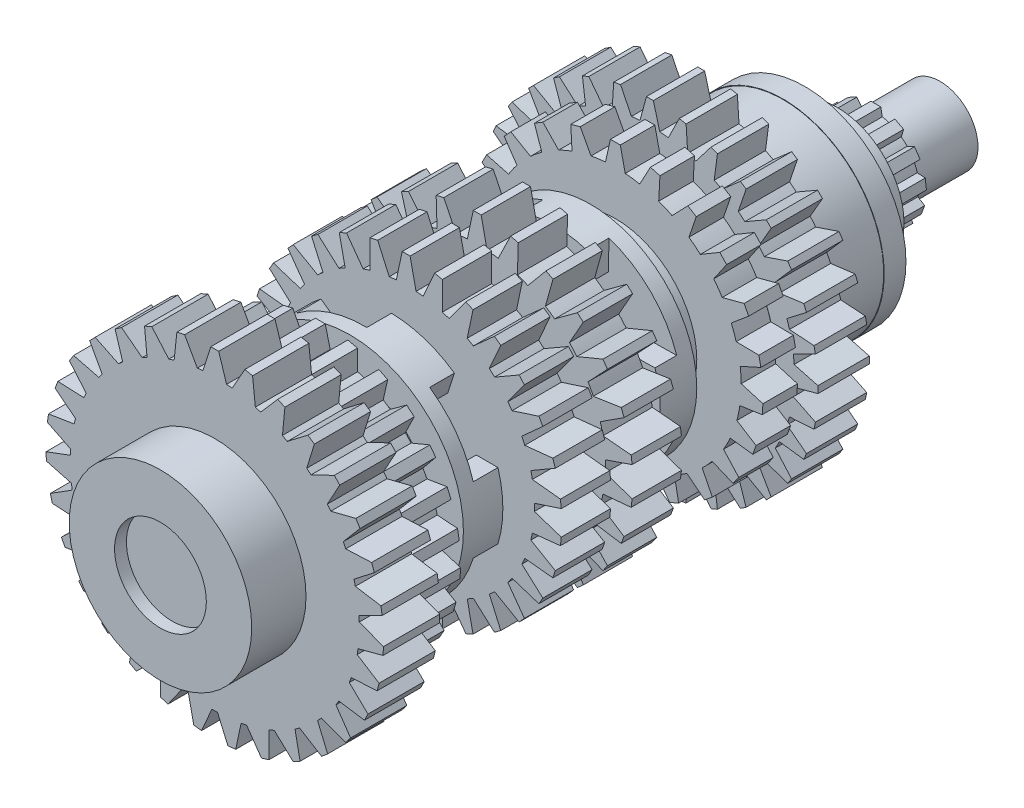
SolidWorks part; units mm, degrees
material "Plain Carbon Steel"
ref_plane "Front Plane" through (0, 0, 0) normal (0, 0, 1) x (1, 0, 0)
ref_plane "Top Plane" through (0, 0, 0) normal (0, 1, 0) x (1, 0, 0)
ref_plane "Right Plane" through (0, 0, 0) normal (1, 0, 0) x (0, 0, -1)
sketch "Sketch1" plane through (0, 0, 0) normal (0, 0, 1) x (1, 0, 0)
  circle A0 centre (0, 0) radius 9.779
  dimension "D1" = 19.558
extrude "Boss-Extrude1" add sketch "Sketch1" along normal blind 16.51
sketch "Sketch2" plane through (0, 0, 16.51) normal (0, 0, 1) x (1, 0, 0)
  line L0 (-1.651, 10.925) -> (-1.27, 12.957)
  line L1 (-1.27, 12.957) -> (1.27, 12.957)
  line L2 (1.27, 12.957) -> (1.651, 10.925)
  line L3 (0, 0) -> (0, 25.9139) construction
  line L4 (3.6152, 10.4408) -> (4.8969, 12.063)
  line L5 (4.8969, 12.063) -> (7.1459, 10.8826)
  line L6 (7.1459, 10.8826) -> (6.539, 8.9063)
  line L7 (8.0532, 7.5648) -> (9.9419, 8.4056)
  line L8 (9.9419, 8.4056) -> (11.3848, 6.3152)
  line L9 (11.3848, 6.3152) -> (9.9289, 4.8473)
  line L10 (10.6463, 2.9558) -> (12.7094, 2.8225)
  line L11 (12.7094, 2.8225) -> (13.0156, 0.301)
  line L12 (13.0156, 0.301) -> (11.0443, -0.3221)
  line L13 (10.8005, -2.3303) -> (12.5653, -3.4071)
  line L14 (12.5653, -3.4071) -> (11.6646, -5.7821)
  line L15 (11.6646, -5.7821) -> (9.6296, -5.4178)
  line L16 (8.4804, -7.0826) -> (9.5427, -8.8563)
  line L17 (9.5427, -8.8563) -> (7.6414, -10.5406)
  line L18 (7.6414, -10.5406) -> (6.0088, -9.2723)
  line L19 (4.2175, -10.2124) -> (4.3339, -12.2765)
  line L20 (4.3339, -12.2765) -> (1.8677, -12.8844)
  line L21 (1.8677, -12.8844) -> (1.0115, -11.0026)
  line L22 (-1.0115, -11.0026) -> (-1.8677, -12.8844)
  line L23 (-1.8677, -12.8844) -> (-4.3339, -12.2765)
  line L24 (-4.3339, -12.2765) -> (-4.2175, -10.2124)
  line L25 (-6.0088, -9.2723) -> (-7.6414, -10.5406)
  line L26 (-7.6414, -10.5406) -> (-9.5427, -8.8563)
  line L27 (-9.5427, -8.8563) -> (-8.4804, -7.0826)
  line L28 (-9.6296, -5.4178) -> (-11.6646, -5.7821)
  line L29 (-11.6646, -5.7821) -> (-12.5653, -3.4071)
  line L30 (-12.5653, -3.4071) -> (-10.8005, -2.3303)
  line L31 (-11.0443, -0.3221) -> (-13.0156, 0.301)
  line L32 (-13.0156, 0.301) -> (-12.7094, 2.8225)
  line L33 (-12.7094, 2.8225) -> (-10.6463, 2.9558)
  line L34 (-9.9289, 4.8473) -> (-11.3848, 6.3152)
  line L35 (-11.3848, 6.3152) -> (-9.9419, 8.4056)
  line L36 (-9.9419, 8.4056) -> (-8.0532, 7.5648)
  line L37 (-6.539, 8.9063) -> (-7.1459, 10.8826)
  line L38 (-7.1459, 10.8826) -> (-4.8969, 12.063)
  line L39 (-4.8969, 12.063) -> (-3.6152, 10.4408)
  arc A0 (-1.651, 10.925) -> (-3.6152, 10.4408) centre (0, 0) ccw
  circle A1 centre (0, 0) radius 9.779 construction
  arc A2 (3.6152, 10.4408) -> (1.651, 10.925) centre (0, 0) ccw
  arc A3 (8.0532, 7.5648) -> (6.539, 8.9063) centre (0, 0) ccw
  arc A4 (10.6463, 2.9558) -> (9.9289, 4.8473) centre (0, 0) ccw
  arc A5 (10.8005, -2.3303) -> (11.0443, -0.3221) centre (0, 0) ccw
  arc A6 (8.4804, -7.0826) -> (9.6296, -5.4178) centre (0, 0) ccw
  arc A7 (4.2175, -10.2124) -> (6.0088, -9.2723) centre (0, 0) ccw
  arc A8 (-1.0115, -11.0026) -> (1.0115, -11.0026) centre (0, 0) ccw
  arc A9 (-6.0088, -9.2723) -> (-4.2175, -10.2124) centre (0, 0) ccw
  arc A10 (-9.6296, -5.4178) -> (-8.4804, -7.0826) centre (0, 0) ccw
  arc A11 (-11.0443, -0.3221) -> (-10.8005, -2.3303) centre (0, 0) ccw
  arc A12 (-9.9289, 4.8473) -> (-10.6463, 2.9558) centre (0, 0) ccw
  arc A13 (-6.539, 8.9063) -> (-8.0532, 7.5648) centre (0, 0) ccw
  point P12 (0, 12.957)
  point P62 (0, 0)
  dimension "D1" = 1.27
  dimension "D2" = 1.651
  dimension "D3" = 2.54
  dimension "D4" = 2.032
  dimension "D5" = 1.651
  dimension "D6" = 13
extrude "Boss-Extrude2" add sketch "Sketch2" along normal blind 9.906
sketch "Sketch3" plane through (0, 0, 26.416) normal (0, 0, 1) x (1, 0, 0)
  circle A0 centre (0, 0) radius 17.145
  dimension "D1" = 34.29
extrude "Boss-Extrude3" add sketch "Sketch3" along normal blind 13.97
ref_plane "Plane1" through (0, 0, 34.798) normal (0, 0, 1) x (1, 0, 0)
sketch "Sketch4" plane through (0, 0, 34.798) normal (0, 0, 1) x (1, 0, 0)
  circle A0 centre (0, 0) radius 17.145
  circle A1 centre (0, 0) radius 26.035
  dimension "D1" = 52.07
  dimension "D2" = 34.29
extrude "Boss-Extrude4" add sketch "Sketch4" along normal blind 5.588
sketch "Sketch5" plane through (0, 0, 40.386) normal (0, 0, 1) x (1, 0, 0)
  circle A0 centre (0, 0) radius 25.908
  dimension "D1" = 51.816
extrude "Boss-Extrude5" add sketch "Sketch5" along normal blind 19.05
sketch "Sketch6" plane through (0, 0, 59.436) normal (0, 0, 1) x (1, 0, 0)
  circle A0 centre (0, 0) radius 17.78
  dimension "D1" = 35.56
extrude "Boss-Extrude6" add sketch "Sketch6" along normal blind 2.032
sketch "Sketch8" plane through (0, 0, 61.468) normal (0, 0, 1) x (1, 0, 0)
  line L0 (0, 0) -> (0, 86.5116) construction
  line L1 (0, -28.6385) -> (0, 28.6385) construction
  line L2 (-2.54, 37.1242) -> (-0.889, 43.2558)
  line L3 (-0.889, 43.2558) -> (0.889, 43.2558)
  line L4 (0.889, 43.2558) -> (2.54, 37.1242)
  line L5 (4.7514, 36.9064) -> (7.5669, 42.5981)
  line L6 (9.3107, 42.2512) -> (9.7338, 35.9153)
  line L7 (7.5669, 42.5981) -> (9.3107, 42.2512)
  line L8 (11.8602, 35.2703) -> (15.732, 40.3034)
  line L9 (17.3746, 39.623) -> (16.5535, 33.3263)
  line L10 (15.732, 40.3034) -> (17.3746, 39.623)
  line L11 (18.5132, 32.2788) -> (23.2925, 36.4598)
  line L12 (24.7708, 35.472) -> (22.737, 29.4565)
  line L13 (23.2925, 36.4598) -> (24.7708, 35.472)
  line L14 (24.4547, 28.0468) -> (29.9579, 31.2151)
  line L15 (31.2151, 29.9579) -> (28.0468, 24.4547)
  line L16 (29.9579, 31.2151) -> (31.2151, 29.9579)
  line L17 (29.4565, 22.737) -> (35.472, 24.7708)
  line L18 (36.4598, 23.2925) -> (32.2788, 18.5132)
  line L19 (35.472, 24.7708) -> (36.4598, 23.2925)
  line L20 (33.3263, 16.5535) -> (39.623, 17.3746)
  line L21 (40.3034, 15.732) -> (35.2703, 11.8602)
  line L22 (39.623, 17.3746) -> (40.3034, 15.732)
  line L23 (35.9153, 9.7338) -> (42.2512, 9.3107)
  line L24 (42.5981, 7.5669) -> (36.9064, 4.7514)
  line L25 (42.2512, 9.3107) -> (42.5981, 7.5669)
  line L26 (37.1242, 2.54) -> (43.2558, 0.889)
  line L27 (43.2558, -0.889) -> (37.1242, -2.54)
  line L28 (43.2558, 0.889) -> (43.2558, -0.889)
  line L29 (36.9064, -4.7514) -> (42.5981, -7.5669)
  line L30 (42.2512, -9.3107) -> (35.9153, -9.7338)
  line L31 (42.5981, -7.5669) -> (42.2512, -9.3107)
  line L32 (35.2703, -11.8602) -> (40.3034, -15.732)
  line L33 (39.623, -17.3746) -> (33.3263, -16.5535)
  line L34 (40.3034, -15.732) -> (39.623, -17.3746)
  line L35 (32.2788, -18.5132) -> (36.4598, -23.2925)
  line L36 (35.472, -24.7708) -> (29.4565, -22.737)
  line L37 (36.4598, -23.2925) -> (35.472, -24.7708)
  line L38 (28.0468, -24.4547) -> (31.2151, -29.9579)
  line L39 (29.9579, -31.2151) -> (24.4547, -28.0468)
  line L40 (31.2151, -29.9579) -> (29.9579, -31.2151)
  line L41 (22.737, -29.4565) -> (24.7708, -35.472)
  line L42 (23.2925, -36.4598) -> (18.5132, -32.2788)
  line L43 (24.7708, -35.472) -> (23.2925, -36.4598)
  line L44 (16.5535, -33.3263) -> (17.3746, -39.623)
  line L45 (15.732, -40.3034) -> (11.8602, -35.2703)
  line L46 (17.3746, -39.623) -> (15.732, -40.3034)
  line L47 (9.7338, -35.9153) -> (9.3107, -42.2512)
  line L48 (7.5669, -42.5981) -> (4.7514, -36.9064)
  line L49 (9.3107, -42.2512) -> (7.5669, -42.5981)
  line L50 (2.54, -37.1242) -> (0.889, -43.2558)
  line L51 (-0.889, -43.2558) -> (-2.54, -37.1242)
  line L52 (0.889, -43.2558) -> (-0.889, -43.2558)
  line L53 (-4.7514, -36.9064) -> (-7.5669, -42.5981)
  line L54 (-9.3107, -42.2512) -> (-9.7338, -35.9153)
  line L55 (-7.5669, -42.5981) -> (-9.3107, -42.2512)
  line L56 (-11.8602, -35.2703) -> (-15.732, -40.3034)
  line L57 (-17.3746, -39.623) -> (-16.5535, -33.3263)
  line L58 (-15.732, -40.3034) -> (-17.3746, -39.623)
  line L59 (-18.5132, -32.2788) -> (-23.2925, -36.4598)
  line L60 (-24.7708, -35.472) -> (-22.737, -29.4565)
  line L61 (-23.2925, -36.4598) -> (-24.7708, -35.472)
  line L62 (-24.4547, -28.0468) -> (-29.9579, -31.2151)
  line L63 (-31.2151, -29.9579) -> (-28.0468, -24.4547)
  line L64 (-29.9579, -31.2151) -> (-31.2151, -29.9579)
  line L65 (-29.4565, -22.737) -> (-35.472, -24.7708)
  line L66 (-36.4598, -23.2925) -> (-32.2788, -18.5132)
  line L67 (-35.472, -24.7708) -> (-36.4598, -23.2925)
  line L68 (-33.3263, -16.5535) -> (-39.623, -17.3746)
  line L69 (-40.3034, -15.732) -> (-35.2703, -11.8602)
  line L70 (-39.623, -17.3746) -> (-40.3034, -15.732)
  line L71 (-35.9153, -9.7338) -> (-42.2512, -9.3107)
  line L72 (-42.5981, -7.5669) -> (-36.9064, -4.7514)
  line L73 (-42.2512, -9.3107) -> (-42.5981, -7.5669)
  line L74 (-37.1242, -2.54) -> (-43.2558, -0.889)
  line L75 (-43.2558, 0.889) -> (-37.1242, 2.54)
  line L76 (-43.2558, -0.889) -> (-43.2558, 0.889)
  line L77 (-36.9064, 4.7514) -> (-42.5981, 7.5669)
  line L78 (-42.2512, 9.3107) -> (-35.9153, 9.7338)
  line L79 (-42.5981, 7.5669) -> (-42.2512, 9.3107)
  line L80 (-35.2703, 11.8602) -> (-40.3034, 15.732)
  line L81 (-39.623, 17.3746) -> (-33.3263, 16.5535)
  line L82 (-40.3034, 15.732) -> (-39.623, 17.3746)
  line L83 (-32.2788, 18.5132) -> (-36.4598, 23.2925)
  line L84 (-35.472, 24.7708) -> (-29.4565, 22.737)
  line L85 (-36.4598, 23.2925) -> (-35.472, 24.7708)
  line L86 (-28.0468, 24.4547) -> (-31.2151, 29.9579)
  line L87 (-29.9579, 31.2151) -> (-24.4547, 28.0468)
  line L88 (-31.2151, 29.9579) -> (-29.9579, 31.2151)
  line L89 (-22.737, 29.4565) -> (-24.7708, 35.472)
  line L90 (-23.2925, 36.4598) -> (-18.5132, 32.2788)
  line L91 (-24.7708, 35.472) -> (-23.2925, 36.4598)
  line L92 (-16.5535, 33.3263) -> (-17.3746, 39.623)
  line L93 (-15.732, 40.3034) -> (-11.8602, 35.2703)
  line L94 (-17.3746, 39.623) -> (-15.732, 40.3034)
  line L95 (-9.7338, 35.9153) -> (-9.3107, 42.2512)
  line L96 (-7.5669, 42.5981) -> (-4.7514, 36.9064)
  line L97 (-9.3107, 42.2512) -> (-7.5669, 42.5981)
  arc A0 (-2.54, 37.1242) -> (-4.7514, 36.9064) centre (0, 0) ccw
  arc A1 (4.7514, 36.9064) -> (2.54, 37.1242) centre (0, 0) ccw
  arc A2 (11.8602, 35.2703) -> (9.7338, 35.9153) centre (0, 0) ccw
  arc A3 (18.5132, 32.2788) -> (16.5535, 33.3263) centre (0, 0) ccw
  arc A4 (24.4547, 28.0468) -> (22.737, 29.4565) centre (0, 0) ccw
  arc A5 (-9.7338, 35.9153) -> (-11.8602, 35.2703) centre (0, 0) ccw
  arc A6 (-16.5535, 33.3263) -> (-18.5132, 32.2788) centre (0, 0) ccw
  arc A7 (-22.737, 29.4565) -> (-24.4547, 28.0468) centre (0, 0) ccw
  arc A8 (-28.0468, 24.4547) -> (-29.4565, 22.737) centre (0, 0) ccw
  arc A9 (-32.2788, 18.5132) -> (-33.3263, 16.5535) centre (0, 0) ccw
  arc A10 (-35.2703, 11.8602) -> (-35.9153, 9.7338) centre (0, 0) ccw
  arc A11 (-36.9064, 4.7514) -> (-37.1242, 2.54) centre (0, 0) ccw
  arc A12 (-37.1242, -2.54) -> (-36.9064, -4.7514) centre (0, 0) ccw
  arc A13 (-35.9153, -9.7338) -> (-35.2703, -11.8602) centre (0, 0) ccw
  arc A14 (-33.3263, -16.5535) -> (-32.2788, -18.5132) centre (0, 0) ccw
  arc A15 (-29.4565, -22.737) -> (-28.0468, -24.4547) centre (0, 0) ccw
  arc A16 (-24.4547, -28.0468) -> (-22.737, -29.4565) centre (0, 0) ccw
  arc A17 (-18.5132, -32.2788) -> (-16.5535, -33.3263) centre (0, 0) ccw
  arc A18 (-11.8602, -35.2703) -> (-9.7338, -35.9153) centre (0, 0) ccw
  arc A19 (-4.7514, -36.9064) -> (-2.54, -37.1242) centre (0, 0) ccw
  arc A20 (2.54, -37.1242) -> (4.7514, -36.9064) centre (0, 0) ccw
  arc A21 (9.7338, -35.9153) -> (11.8602, -35.2703) centre (0, 0) ccw
  arc A22 (16.5535, -33.3263) -> (18.5132, -32.2788) centre (0, 0) ccw
  arc A23 (22.737, -29.4565) -> (24.4547, -28.0468) centre (0, 0) ccw
  arc A24 (28.0468, -24.4547) -> (29.4565, -22.737) centre (0, 0) ccw
  arc A25 (32.2788, -18.5132) -> (33.3263, -16.5535) centre (0, 0) ccw
  arc A26 (35.2703, -11.8602) -> (35.9153, -9.7338) centre (0, 0) ccw
  arc A27 (36.9064, -4.7514) -> (37.1242, -2.54) centre (0, 0) ccw
  arc A28 (37.1242, 2.54) -> (36.9064, 4.7514) centre (0, 0) ccw
  arc A29 (35.9153, 9.7338) -> (35.2703, 11.8602) centre (0, 0) ccw
  arc A30 (33.3263, 16.5535) -> (32.2788, 18.5132) centre (0, 0) ccw
  arc A31 (29.4565, 22.737) -> (28.0468, 24.4547) centre (0, 0) ccw
  point P8 (0, 43.2558)
  point P138 (0, 0)
  dimension "D1" = 74.422
  dimension "D2" = 2.54
  dimension "D3" = 2.54
  dimension "D4" = 1.778
  dimension "D5" = 6.35
  dimension "D6" = 32
extrude "Boss-Extrude7" add sketch "Sketch8" along normal blind 13.208
sketch "Sketch10" plane through (0, 0, 74.676) normal (0, 0, 1) x (1, 0, 0)
  line L0 (-12.7, 27.0822) -> (-8.89, 19.05)
  line L1 (8.89, 19.05) -> (12.7, 27.0822)
  line L2 (0, 0) -> (0, 67.7318) construction
  line L3 (0, -41.0718) -> (0, 41.0718) construction
  line L4 (21.8322, 20.4473) -> (15.3705, 14.3417)
  line L5 (20.8648, -2.5681) -> (29.6812, -3.7096)
  line L6 (26.193, -14.4451) -> (18.3895, -10.1864)
  line L7 (4.0051, -20.6372) -> (5.644, -29.3748)
  line L8 (-5.644, -29.3748) -> (-4.0051, -20.6372)
  line L9 (-18.3895, -10.1864) -> (-26.193, -14.4451)
  line L10 (-29.6812, -3.7096) -> (-20.8648, -2.5681)
  line L11 (-15.3705, 14.3417) -> (-21.8322, 20.4473)
  arc A3 (-8.89, 19.05) -> (8.89, 19.05) centre (0, -7.438) cw
  arc A4 (-12.7, 27.0822) -> (12.7, 27.0822) centre (0, 14.6388) cw
  arc A5 (21.8322, 20.4473) -> (29.6812, -3.7096) centre (13.9223, 4.5236) cw
  arc A6 (15.3705, 14.3417) -> (20.8648, -2.5681) centre (-7.0739, -2.2985) cw
  arc A7 (26.193, -14.4451) -> (5.644, -29.3748) centre (8.6045, -11.843) cw
  arc A8 (18.3895, -10.1864) -> (4.0051, -20.6372) centre (-4.3719, 6.0174) cw
  arc A9 (-5.644, -29.3748) -> (-26.193, -14.4451) centre (-8.6045, -11.843) cw
  arc A10 (-4.0051, -20.6372) -> (-18.3895, -10.1864) centre (4.3719, 6.0174) cw
  arc A11 (-29.6812, -3.7096) -> (-21.8322, 20.4473) centre (-13.9223, 4.5236) cw
  arc A12 (-20.8648, -2.5681) -> (-15.3705, 14.3417) centre (7.0739, -2.2985) cw
  point P5 (0, 20.502)
  point P39 (0, 0)
  dimension "D3" = 19.05
  dimension "D4" = 17.78
  dimension "D5" = 27.94
  dimension "D1" = 8.89
  dimension "D2" = 8.89
  dimension "D6" = 17.78
  dimension "D7" = 25.4
  dimension "D8" = 5
extrude "Cut-Extrude1" cut sketch "Sketch10" against normal up to surface (13.208 mm away) up to face at (17.78, 0, 61.468)
sketch "Sketch12" plane through (0, 0, 74.676) normal (0, 0, 1) x (1, 0, 0)
  line L0 (-2.54, 32.2852) -> (-1.27, 37.9875)
  line L1 (-1.27, 37.9875) -> (1.27, 37.9875)
  line L2 (1.27, 37.9875) -> (2.54, 32.2852)
  line L3 (0, 0) -> (0, 75.975) construction
  line L4 (11.4718, 36.2362) -> (11.1563, 30.4027)
  line L5 (6.2646, 31.7733) -> (9.026, 36.9215)
  line L6 (9.026, 36.9215) -> (11.4718, 36.2362)
  line L7 (20.8228, 31.7974) -> (18.9451, 26.2654)
  line L8 (14.6047, 28.9049) -> (18.6526, 33.1171)
  line L9 (18.6526, 33.1171) -> (20.8228, 31.7974)
  line L10 (28.6295, 25.0003) -> (25.3289, 20.1801)
  line L11 (21.8615, 23.8927) -> (26.8958, 26.8567)
  line L12 (26.8958, 26.8567) -> (28.6295, 25.0003)
  line L13 (34.3128, 16.3491) -> (29.8342, 12.5981)
  line L14 (27.497, 17.1085) -> (33.1443, 18.6043)
  line L15 (33.1443, 18.6043) -> (34.3128, 16.3491)
  line L16 (37.4514, 6.4854) -> (32.1267, 4.0818)
  line L17 (31.0932, 9.0555) -> (36.9346, 8.9722)
  line L18 (36.9346, 8.9722) -> (37.4514, 6.4854)
  line L19 (37.8123, -3.8594) -> (32.0366, -4.7373)
  line L20 (32.3833, 0.3309) -> (37.9856, -1.3253)
  line L21 (37.9856, -1.3253) -> (37.8123, -3.8594)
  line L22 (35.3689, -13.9179) -> (29.5705, -13.205)
  line L23 (31.2717, -8.4183) -> (36.2195, -11.5246)
  line L24 (36.2195, -11.5246) -> (35.3689, -13.9179)
  line L25 (30.3023, -22.9442) -> (24.9113, -20.6934)
  line L26 (27.8408, -16.5432) -> (31.767, -20.8691)
  line L27 (31.767, -20.8691) -> (30.3023, -22.9442)
  line L28 (22.9883, -30.2688) -> (18.4045, -26.647)
  line L29 (22.3451, -23.4411) -> (24.9586, -28.6659)
  line L30 (24.9586, -28.6659) -> (22.9883, -30.2688)
  line L31 (13.9694, -35.3486) -> (10.5328, -30.6243)
  line L32 (15.1922, -28.6004) -> (16.2991, -34.3366)
  line L33 (16.2991, -34.3366) -> (13.9694, -35.3486)
  line L34 (3.9145, -37.8066) -> (1.8798, -32.3304)
  line L35 (6.9125, -31.6387) -> (6.4308, -37.4608)
  line L36 (6.4308, -37.4608) -> (3.9145, -37.8066)
  line L37 (-6.4308, -37.4608) -> (-6.9125, -31.6387)
  line L38 (-1.8798, -32.3304) -> (-3.9145, -37.8066)
  line L39 (-3.9145, -37.8066) -> (-6.4308, -37.4608)
  line L40 (-16.2991, -34.3366) -> (-15.1922, -28.6004)
  line L41 (-10.5328, -30.6243) -> (-13.9694, -35.3486)
  line L42 (-13.9694, -35.3486) -> (-16.2991, -34.3366)
  line L43 (-24.9586, -28.6659) -> (-22.3451, -23.4411)
  line L44 (-18.4045, -26.647) -> (-22.9883, -30.2688)
  line L45 (-22.9883, -30.2688) -> (-24.9586, -28.6659)
  line L46 (-31.767, -20.8691) -> (-27.8408, -16.5432)
  line L47 (-24.9113, -20.6934) -> (-30.3023, -22.9442)
  line L48 (-30.3023, -22.9442) -> (-31.767, -20.8691)
  line L49 (-36.2195, -11.5246) -> (-31.2717, -8.4183)
  line L50 (-29.5705, -13.205) -> (-35.3689, -13.9179)
  line L51 (-35.3689, -13.9179) -> (-36.2195, -11.5246)
  line L52 (-37.9856, -1.3253) -> (-32.3833, 0.3309)
  line L53 (-32.0366, -4.7373) -> (-37.8123, -3.8594)
  line L54 (-37.8123, -3.8594) -> (-37.9856, -1.3253)
  line L55 (-36.9346, 8.9722) -> (-31.0932, 9.0555)
  line L56 (-32.1267, 4.0818) -> (-37.4514, 6.4854)
  line L57 (-37.4514, 6.4854) -> (-36.9346, 8.9722)
  line L58 (-33.1443, 18.6043) -> (-27.497, 17.1085)
  line L59 (-29.8342, 12.5981) -> (-34.3128, 16.3491)
  line L60 (-34.3128, 16.3491) -> (-33.1443, 18.6043)
  line L61 (-26.8958, 26.8567) -> (-21.8615, 23.8927)
  line L62 (-25.3289, 20.1801) -> (-28.6295, 25.0003)
  line L63 (-28.6295, 25.0003) -> (-26.8958, 26.8567)
  line L64 (-18.6526, 33.1171) -> (-14.6047, 28.9049)
  line L65 (-18.9451, 26.2654) -> (-20.8228, 31.7974)
  line L66 (-20.8228, 31.7974) -> (-18.6526, 33.1171)
  line L67 (-9.026, 36.9215) -> (-6.2646, 31.7733)
  line L68 (-11.1563, 30.4027) -> (-11.4718, 36.2362)
  line L69 (-11.4718, 36.2362) -> (-9.026, 36.9215)
  arc A0 (-2.54, 32.2852) -> (-6.2646, 31.7733) centre (0, 0) ccw
  arc A1 (6.2646, 31.7733) -> (2.54, 32.2852) centre (0, 0) ccw
  arc A2 (14.6047, 28.9049) -> (11.1563, 30.4027) centre (0, 0) ccw
  arc A3 (21.8615, 23.8927) -> (18.9451, 26.2654) centre (0, 0) ccw
  arc A4 (27.497, 17.1085) -> (25.3289, 20.1801) centre (0, 0) ccw
  arc A5 (31.0932, 9.0555) -> (29.8342, 12.5981) centre (0, 0) ccw
  arc A6 (32.3833, 0.3309) -> (32.1267, 4.0818) centre (0, 0) ccw
  arc A7 (31.2717, -8.4183) -> (32.0366, -4.7373) centre (0, 0) ccw
  arc A8 (27.8408, -16.5432) -> (29.5705, -13.205) centre (0, 0) ccw
  arc A9 (22.3451, -23.4411) -> (24.9113, -20.6934) centre (0, 0) ccw
  arc A10 (15.1922, -28.6004) -> (18.4045, -26.647) centre (0, 0) ccw
  arc A11 (6.9125, -31.6387) -> (10.5328, -30.6243) centre (0, 0) ccw
  arc A12 (-1.8798, -32.3304) -> (1.8798, -32.3304) centre (0, 0) ccw
  arc A13 (-10.5328, -30.6243) -> (-6.9125, -31.6387) centre (0, 0) ccw
  arc A14 (-18.4045, -26.647) -> (-15.1922, -28.6004) centre (0, 0) ccw
  arc A15 (-24.9113, -20.6934) -> (-22.3451, -23.4411) centre (0, 0) ccw
  arc A16 (-29.5705, -13.205) -> (-27.8408, -16.5432) centre (0, 0) ccw
  arc A17 (-32.0366, -4.7373) -> (-31.2717, -8.4183) centre (0, 0) ccw
  arc A18 (-32.1267, 4.0818) -> (-32.3833, 0.3309) centre (0, 0) ccw
  arc A19 (-29.8342, 12.5981) -> (-31.0932, 9.0555) centre (0, 0) ccw
  arc A20 (-25.3289, 20.1801) -> (-27.497, 17.1085) centre (0, 0) ccw
  arc A21 (-18.9451, 26.2654) -> (-21.8615, 23.8927) centre (0, 0) ccw
  arc A22 (-11.1563, 30.4027) -> (-14.6047, 28.9049) centre (0, 0) ccw
  point P5 (0, 37.9875)
  point P100 (0, 0)
  dimension "D1" = 64.77
  dimension "D2" = 2.54
  dimension "D3" = 2.54
  dimension "D4" = 2.54
  dimension "D5" = 5.842
  dimension "D6" = 23
extrude "Boss-Extrude8" add sketch "Sketch12" along normal blind 8.89
sketch "Sketch13" plane through (0, 0, 83.566) normal (0, 0, 1) x (1, 0, 0)
  circle A0 centre (0, 0) radius 20.955
  dimension "D1" = 41.91
extrude "Boss-Extrude9" add sketch "Sketch13" along normal blind 6.35
sketch "Sketch14" plane through (0, 0, 89.916) normal (0, 0, 1) x (1, 0, 0)
  circle A0 centre (0, 0) radius 27.305
  dimension "D1" = 54.61
extrude "Boss-Extrude10" add sketch "Sketch14" along normal blind 3.81
sketch "Sketch15" plane through (0, 0, 93.726) normal (0, 0, 1) x (1, 0, 0)
  line L0 (-8.382, 18.3253) -> (8.382, 18.3253)
  line L1 (8.382, 18.3253) -> (8.509, 25.9453)
  line L2 (0, 0) -> (0, 51.2544) construction
  line L3 (-8.382, 18.3253) -> (-8.509, 25.9453)
  line L4 (18.3253, -8.382) -> (25.9453, -8.509)
  line L5 (18.3253, 8.382) -> (18.3253, -8.382)
  line L6 (18.3253, 8.382) -> (25.9453, 8.509)
  line L7 (-8.382, -18.3253) -> (-8.509, -25.9453)
  line L8 (8.382, -18.3253) -> (-8.382, -18.3253)
  line L9 (8.382, -18.3253) -> (8.509, -25.9453)
  line L10 (-18.3253, 8.382) -> (-25.9453, 8.509)
  line L11 (-18.3253, -8.382) -> (-18.3253, 8.382)
  line L12 (-18.3253, -8.382) -> (-25.9453, -8.509)
  circle A0 centre (0, 0) radius 27.305 construction
  arc A1 (8.509, 25.9453) -> (-8.509, 25.9453) centre (0, 0) ccw
  arc A2 (25.9453, -8.509) -> (25.9453, 8.509) centre (0, 0) ccw
  arc A3 (-8.509, -25.9453) -> (8.509, -25.9453) centre (0, 0) ccw
  arc A4 (-25.9453, 8.509) -> (-25.9453, -8.509) centre (0, 0) ccw
  point P4 (0, 18.3253)
  point P23 (0, 0)
  dimension "D1" = 7.62
  dimension "D2" = 7.62
  dimension "D3" = 8.509
  dimension "D4" = 16.764
  dimension "D5" = 4
extrude "Boss-Extrude11" add sketch "Sketch15" along normal blind 5.588
sketch "Sketch16" plane through (0, 0, 93.726) normal (0, 0, 1) x (1, 0, 0)
  circle A0 centre (0, 0) radius 13.335
  dimension "D1" = 26.67
extrude "Boss-Extrude12" add sketch "Sketch16" along normal blind 12.7
sketch "Sketch17" plane through (0, 0, 106.426) normal (0, 0, 1) x (1, 0, 0)
  line L0 (0, 0) -> (0, 56.1959) construction
  line L1 (-2.54, 32.9222) -> (-1.016, 40.0342)
  line L2 (-1.016, 40.0342) -> (1.016, 40.0342)
  line L3 (1.016, 40.0342) -> (2.54, 32.9222)
  line L4 (10.5673, 38.6277) -> (10.345, 31.3576)
  line L5 (5.4126, 32.5734) -> (8.5943, 39.114)
  line L6 (8.5943, 39.114) -> (10.5673, 38.6277)
  line L7 (19.5044, 34.9763) -> (17.5488, 27.9707)
  line L8 (13.0506, 30.3315) -> (17.7052, 35.9206)
  line L9 (17.7052, 35.9206) -> (19.5044, 34.9763)
  line L10 (27.308, 29.2923) -> (23.7326, 22.9583)
  line L11 (19.9302, 26.3269) -> (25.7871, 30.6397)
  line L12 (25.7871, 30.6397) -> (27.308, 29.2923)
  line L13 (33.5246, 21.9058) -> (28.5373, 16.6115)
  line L14 (25.6515, 20.7923) -> (32.3703, 23.5781)
  line L15 (32.3703, 23.5781) -> (33.5246, 21.9058)
  line L16 (37.7929, 13.2463) -> (31.6835, 9.2994)
  line L17 (29.8821, 14.0493) -> (37.0723, 15.1463)
  line L18 (37.0723, 15.1463) -> (37.7929, 13.2463)
  line L19 (39.8647, 3.817) -> (32.9883, 1.4468)
  line L20 (32.376, 6.4898) -> (39.6198, 5.8342)
  line L21 (39.6198, 5.8342) -> (39.8647, 3.817)
  line L22 (39.6198, -5.8342) -> (32.376, -6.4898)
  line L23 (32.9883, -1.4468) -> (39.8647, -3.817)
  line L24 (39.8647, -3.817) -> (39.6198, -5.8342)
  line L25 (37.0723, -15.1463) -> (29.8821, -14.0493)
  line L26 (31.6835, -9.2994) -> (37.7929, -13.2463)
  line L27 (37.7929, -13.2463) -> (37.0723, -15.1463)
  line L28 (32.3703, -23.5781) -> (25.6515, -20.7923)
  line L29 (28.5373, -16.6115) -> (33.5246, -21.9058)
  line L30 (33.5246, -21.9058) -> (32.3703, -23.5781)
  line L31 (25.7871, -30.6397) -> (19.9302, -26.3269)
  line L32 (23.7326, -22.9583) -> (27.308, -29.2923)
  line L33 (27.308, -29.2923) -> (25.7871, -30.6397)
  line L34 (17.7052, -35.9206) -> (13.0506, -30.3315)
  line L35 (17.5488, -27.9707) -> (19.5044, -34.9763)
  line L36 (19.5044, -34.9763) -> (17.7052, -35.9206)
  line L37 (8.5943, -39.114) -> (5.4126, -32.5734)
  line L38 (10.345, -31.3576) -> (10.5673, -38.6277)
  line L39 (10.5673, -38.6277) -> (8.5943, -39.114)
  line L40 (-1.016, -40.0342) -> (-2.54, -32.9222)
  line L41 (2.54, -32.9222) -> (1.016, -40.0342)
  line L42 (1.016, -40.0342) -> (-1.016, -40.0342)
  line L43 (-10.5673, -38.6277) -> (-10.345, -31.3576)
  line L44 (-5.4126, -32.5734) -> (-8.5943, -39.114)
  line L45 (-8.5943, -39.114) -> (-10.5673, -38.6277)
  line L46 (-19.5044, -34.9763) -> (-17.5488, -27.9707)
  line L47 (-13.0506, -30.3315) -> (-17.7052, -35.9206)
  line L48 (-17.7052, -35.9206) -> (-19.5044, -34.9763)
  line L49 (-27.308, -29.2923) -> (-23.7326, -22.9583)
  line L50 (-19.9302, -26.3269) -> (-25.7871, -30.6397)
  line L51 (-25.7871, -30.6397) -> (-27.308, -29.2923)
  line L52 (-33.5246, -21.9058) -> (-28.5373, -16.6115)
  line L53 (-25.6515, -20.7923) -> (-32.3703, -23.5781)
  line L54 (-32.3703, -23.5781) -> (-33.5246, -21.9058)
  line L55 (-37.7929, -13.2463) -> (-31.6835, -9.2994)
  line L56 (-29.8821, -14.0493) -> (-37.0723, -15.1463)
  line L57 (-37.0723, -15.1463) -> (-37.7929, -13.2463)
  line L58 (-39.8647, -3.817) -> (-32.9883, -1.4468)
  line L59 (-32.376, -6.4898) -> (-39.6198, -5.8342)
  line L60 (-39.6198, -5.8342) -> (-39.8647, -3.817)
  line L61 (-39.6198, 5.8342) -> (-32.376, 6.4898)
  line L62 (-32.9883, 1.4468) -> (-39.8647, 3.817)
  line L63 (-39.8647, 3.817) -> (-39.6198, 5.8342)
  line L64 (-37.0723, 15.1463) -> (-29.8821, 14.0493)
  line L65 (-31.6835, 9.2994) -> (-37.7929, 13.2463)
  line L66 (-37.7929, 13.2463) -> (-37.0723, 15.1463)
  line L67 (-32.3703, 23.5781) -> (-25.6515, 20.7923)
  line L68 (-28.5373, 16.6115) -> (-33.5246, 21.9058)
  line L69 (-33.5246, 21.9058) -> (-32.3703, 23.5781)
  line L70 (-25.7871, 30.6397) -> (-19.9302, 26.3269)
  line L71 (-23.7326, 22.9583) -> (-27.308, 29.2923)
  line L72 (-27.308, 29.2923) -> (-25.7871, 30.6397)
  line L73 (-17.7052, 35.9206) -> (-13.0506, 30.3315)
  line L74 (-17.5488, 27.9707) -> (-19.5044, 34.9763)
  line L75 (-19.5044, 34.9763) -> (-17.7052, 35.9206)
  line L76 (-8.5943, 39.114) -> (-5.4126, 32.5734)
  line L77 (-10.345, 31.3576) -> (-10.5673, 38.6277)
  line L78 (-10.5673, 38.6277) -> (-8.5943, 39.114)
  arc A0 (-2.54, 32.9222) -> (-5.4126, 32.5734) centre (0, 0) ccw
  arc A1 (5.4126, 32.5734) -> (2.54, 32.9222) centre (0, 0) ccw
  arc A2 (13.0506, 30.3315) -> (10.345, 31.3576) centre (0, 0) ccw
  arc A3 (19.9302, 26.3269) -> (17.5488, 27.9707) centre (0, 0) ccw
  arc A4 (25.6515, 20.7923) -> (23.7326, 22.9583) centre (0, 0) ccw
  arc A5 (29.8821, 14.0493) -> (28.5373, 16.6115) centre (0, 0) ccw
  arc A6 (32.376, 6.4898) -> (31.6835, 9.2994) centre (0, 0) ccw
  arc A7 (32.9883, -1.4468) -> (32.9883, 1.4468) centre (0, 0) ccw
  arc A8 (31.6835, -9.2994) -> (32.376, -6.4898) centre (0, 0) ccw
  arc A9 (28.5373, -16.6115) -> (29.8821, -14.0493) centre (0, 0) ccw
  arc A10 (23.7326, -22.9583) -> (25.6515, -20.7923) centre (0, 0) ccw
  arc A11 (10.345, -31.3576) -> (13.0506, -30.3315) centre (0, 0) ccw
  arc A12 (2.54, -32.9222) -> (5.4126, -32.5734) centre (0, 0) ccw
  arc A13 (-5.4126, -32.5734) -> (-2.54, -32.9222) centre (0, 0) ccw
  arc A14 (-13.0506, -30.3315) -> (-10.345, -31.3576) centre (0, 0) ccw
  arc A15 (-19.9302, -26.3269) -> (-17.5488, -27.9707) centre (0, 0) ccw
  arc A16 (-25.6515, -20.7923) -> (-23.7326, -22.9583) centre (0, 0) ccw
  arc A17 (-29.8821, -14.0493) -> (-28.5373, -16.6115) centre (0, 0) ccw
  arc A18 (-32.376, -6.4898) -> (-31.6835, -9.2994) centre (0, 0) ccw
  arc A19 (-32.9883, 1.4468) -> (-32.9883, -1.4468) centre (0, 0) ccw
  arc A20 (-31.6835, 9.2994) -> (-32.376, 6.4898) centre (0, 0) ccw
  arc A21 (-28.5373, 16.6115) -> (-29.8821, 14.0493) centre (0, 0) ccw
  arc A22 (-23.7326, 22.9583) -> (-25.6515, 20.7923) centre (0, 0) ccw
  arc A23 (-17.5488, 27.9707) -> (-19.9302, 26.3269) centre (0, 0) ccw
  arc A24 (-10.345, 31.3576) -> (-13.0506, 30.3315) centre (0, 0) ccw
  arc A25 (17.5488, -27.9707) -> (19.9302, -26.3269) centre (0, 0) ccw
  point P6 (0, 40.0342)
  point P112 (0, 0)
  dimension "D1" = 66.04
  dimension "D2" = 2.54
  dimension "D3" = 2.54
  dimension "D4" = 2.032
  dimension "D5" = 7.112
  dimension "D6" = 26
extrude "Boss-Extrude13" add sketch "Sketch17" along normal blind 12.7
sketch "Sketch18" plane through (0, 0, 119.126) normal (0, 0, 1) x (1, 0, 0)
  circle A0 centre (0, 0) radius 19.05
  dimension "D1" = 38.1
extrude "Boss-Extrude14" add sketch "Sketch18" along normal blind 5.588
sketch "Sketch20" plane through (0, 0, 124.714) normal (0, 0, 1) x (1, 0, 0)
  line L0 (-1.016, 40.0342) -> (-2.54, 32.9222) construction
  line L1 (1.016, 40.0342) -> (-1.016, 40.0342) construction
  line L2 (2.54, 32.9222) -> (1.016, 40.0342) construction
  line L3 (-1.016, 40.0342) -> (-2.54, 32.9222)
  line L4 (1.016, 40.0342) -> (-1.016, 40.0342)
  line L5 (2.54, 32.9222) -> (1.016, 40.0342)
  line L6 (9.3294, 31.6746) -> (9.3174, 38.9481)
  line L7 (7.3298, 39.3706) -> (4.3604, 32.7308)
  line L8 (9.3174, 38.9481) -> (7.3298, 39.3706)
  line L9 (15.7111, 29.0428) -> (17.2115, 36.1598)
  line L10 (15.3552, 36.9863) -> (11.0702, 31.109)
  line L11 (17.2115, 36.1598) -> (15.3552, 36.9863)
  line L12 (21.4061, 25.1416) -> (24.3535, 31.7911)
  line L13 (22.7095, 32.9855) -> (17.2963, 28.1276)
  line L14 (24.3535, 31.7911) -> (22.7095, 32.9855)
  line L15 (26.1655, 20.1416) -> (30.431, 26.033)
  line L16 (29.0713, 27.5431) -> (22.7663, 23.9168)
  line L17 (30.431, 26.033) -> (29.0713, 27.5431)
  line L18 (29.7814, 14.2614) -> (35.1786, 19.1372)
  line L19 (34.1626, 20.897) -> (27.2414, 18.6608)
  line L20 (35.1786, 19.1372) -> (34.1626, 20.897)
  line L21 (32.0957, 7.7578) -> (38.3887, 11.405)
  line L22 (37.7608, 13.3375) -> (30.5259, 12.5892)
  line L23 (38.3887, 11.405) -> (37.7608, 13.3375)
  line L24 (33.0073, 0.9152) -> (39.9211, 3.1743)
  line L25 (39.7087, 5.1951) -> (32.4763, 5.9674)
  line L26 (39.9211, 3.1743) -> (39.7087, 5.1951)
  line L27 (32.4763, -5.9674) -> (39.7087, -5.1951)
  line L28 (39.9211, -3.1743) -> (33.0073, -0.9152)
  line L29 (39.7087, -5.1951) -> (39.9211, -3.1743)
  line L30 (30.5259, -12.5892) -> (37.7608, -13.3375)
  line L31 (38.3887, -11.405) -> (32.0957, -7.7578)
  line L32 (37.7608, -13.3375) -> (38.3887, -11.405)
  line L33 (27.2414, -18.6608) -> (34.1626, -20.897)
  line L34 (35.1786, -19.1372) -> (29.7814, -14.2614)
  line L35 (34.1626, -20.897) -> (35.1786, -19.1372)
  line L36 (22.7663, -23.9168) -> (29.0713, -27.5431)
  line L37 (30.431, -26.033) -> (26.1655, -20.1416)
  line L38 (29.0713, -27.5431) -> (30.431, -26.033)
  line L39 (17.2963, -28.1276) -> (22.7095, -32.9855)
  line L40 (24.3535, -31.7911) -> (21.4061, -25.1416)
  line L41 (22.7095, -32.9855) -> (24.3535, -31.7911)
  line L42 (11.0702, -31.109) -> (15.3552, -36.9863)
  line L43 (17.2115, -36.1598) -> (15.7111, -29.0428)
  line L44 (15.3552, -36.9863) -> (17.2115, -36.1598)
  line L45 (4.3604, -32.7308) -> (7.3298, -39.3706)
  line L46 (9.3174, -38.9481) -> (9.3294, -31.6746)
  line L47 (7.3298, -39.3706) -> (9.3174, -38.9481)
  line L48 (-2.54, -32.9222) -> (-1.016, -40.0342)
  line L49 (1.016, -40.0342) -> (2.54, -32.9222)
  line L50 (-1.016, -40.0342) -> (1.016, -40.0342)
  line L51 (-9.3294, -31.6746) -> (-9.3174, -38.9481)
  line L52 (-7.3298, -39.3706) -> (-4.3604, -32.7308)
  line L53 (-9.3174, -38.9481) -> (-7.3298, -39.3706)
  line L54 (-15.7111, -29.0428) -> (-17.2115, -36.1598)
  line L55 (-15.3552, -36.9863) -> (-11.0702, -31.109)
  line L56 (-17.2115, -36.1598) -> (-15.3552, -36.9863)
  line L57 (-21.4061, -25.1416) -> (-24.3535, -31.7911)
  line L58 (-22.7095, -32.9855) -> (-17.2963, -28.1276)
  line L59 (-24.3535, -31.7911) -> (-22.7095, -32.9855)
  line L60 (-26.1655, -20.1416) -> (-30.431, -26.033)
  line L61 (-29.0713, -27.5431) -> (-22.7663, -23.9168)
  line L62 (-30.431, -26.033) -> (-29.0713, -27.5431)
  line L63 (-29.7814, -14.2614) -> (-35.1786, -19.1372)
  line L64 (-34.1626, -20.897) -> (-27.2414, -18.6608)
  line L65 (-35.1786, -19.1372) -> (-34.1626, -20.897)
  line L66 (-32.0957, -7.7578) -> (-38.3887, -11.405)
  line L67 (-37.7608, -13.3375) -> (-30.5259, -12.5892)
  line L68 (-38.3887, -11.405) -> (-37.7608, -13.3375)
  line L69 (-33.0073, -0.9152) -> (-39.9211, -3.1743)
  line L70 (-39.7087, -5.1951) -> (-32.4763, -5.9674)
  line L71 (-39.9211, -3.1743) -> (-39.7087, -5.1951)
  line L72 (-32.4763, 5.9674) -> (-39.7087, 5.1951)
  line L73 (-39.9211, 3.1743) -> (-33.0073, 0.9152)
  line L74 (-39.7087, 5.1951) -> (-39.9211, 3.1743)
  line L75 (-30.5259, 12.5892) -> (-37.7608, 13.3375)
  line L76 (-38.3887, 11.405) -> (-32.0957, 7.7578)
  line L77 (-37.7608, 13.3375) -> (-38.3887, 11.405)
  line L78 (-27.2414, 18.6608) -> (-34.1626, 20.897)
  line L79 (-35.1786, 19.1372) -> (-29.7814, 14.2614)
  line L80 (-34.1626, 20.897) -> (-35.1786, 19.1372)
  line L81 (-22.7663, 23.9168) -> (-29.0713, 27.5431)
  line L82 (-30.431, 26.033) -> (-26.1655, 20.1416)
  line L83 (-29.0713, 27.5431) -> (-30.431, 26.033)
  line L84 (-17.2963, 28.1276) -> (-22.7095, 32.9855)
  line L85 (-24.3535, 31.7911) -> (-21.4061, 25.1416)
  line L86 (-22.7095, 32.9855) -> (-24.3535, 31.7911)
  line L87 (-11.0702, 31.109) -> (-15.3552, 36.9863)
  line L88 (-17.2115, 36.1598) -> (-15.7111, 29.0428)
  line L89 (-15.3552, 36.9863) -> (-17.2115, 36.1598)
  line L90 (-4.3604, 32.7308) -> (-7.3298, 39.3706)
  line L91 (-9.3174, 38.9481) -> (-9.3294, 31.6746)
  line L92 (-7.3298, 39.3706) -> (-9.3174, 38.9481)
  arc A0 (-2.54, 32.9222) -> (-4.3604, 32.7308) centre (0, 0) ccw
  arc A1 (4.3604, 32.7308) -> (2.54, 32.9222) centre (0, 0) ccw
  arc A2 (11.0702, 31.109) -> (9.3294, 31.6746) centre (0, 0) ccw
  arc A3 (17.2963, 28.1276) -> (15.7111, 29.0428) centre (0, 0) ccw
  arc A4 (22.7663, 23.9168) -> (21.4061, 25.1416) centre (0, 0) ccw
  arc A5 (27.2414, 18.6608) -> (26.1655, 20.1416) centre (0, 0) ccw
  arc A6 (30.5259, 12.5892) -> (29.7814, 14.2614) centre (0, 0) ccw
  arc A7 (-9.3294, 31.6746) -> (-11.0702, 31.109) centre (0, 0) ccw
  arc A8 (-15.7111, 29.0428) -> (-17.2963, 28.1276) centre (0, 0) ccw
  arc A9 (-21.4061, 25.1416) -> (-22.7663, 23.9168) centre (0, 0) ccw
  arc A10 (-26.1655, 20.1416) -> (-27.2414, 18.6608) centre (0, 0) ccw
  arc A11 (-29.7814, 14.2614) -> (-30.5259, 12.5892) centre (0, 0) ccw
  arc A12 (-32.0957, 7.7578) -> (-32.4763, 5.9674) centre (0, 0) ccw
  arc A13 (-33.0073, 0.9152) -> (-33.0073, -0.9152) centre (0, 0) ccw
  arc A14 (-32.4763, -5.9674) -> (-32.0957, -7.7578) centre (0, 0) ccw
  arc A15 (-30.5259, -12.5892) -> (-29.7814, -14.2614) centre (0, 0) ccw
  arc A16 (-27.2414, -18.6608) -> (-26.1655, -20.1416) centre (0, 0) ccw
  arc A17 (-22.7663, -23.9168) -> (-21.4061, -25.1416) centre (0, 0) ccw
  arc A18 (-17.2963, -28.1276) -> (-15.7111, -29.0428) centre (0, 0) ccw
  arc A19 (-11.0702, -31.109) -> (-9.3294, -31.6746) centre (0, 0) ccw
  arc A20 (-4.3604, -32.7308) -> (-2.54, -32.9222) centre (0, 0) ccw
  arc A21 (2.54, -32.9222) -> (4.3604, -32.7308) centre (0, 0) ccw
  arc A22 (9.3294, -31.6746) -> (11.0702, -31.109) centre (0, 0) ccw
  arc A23 (21.4061, -25.1416) -> (22.7663, -23.9168) centre (0, 0) ccw
  arc A24 (15.7111, -29.0428) -> (17.2963, -28.1276) centre (0, 0) ccw
  arc A25 (26.1655, -20.1416) -> (27.2414, -18.6608) centre (0, 0) ccw
  arc A26 (29.7814, -14.2614) -> (30.5259, -12.5892) centre (0, 0) ccw
  arc A27 (32.0957, -7.7578) -> (32.4763, -5.9674) centre (0, 0) ccw
  arc A28 (33.0073, -0.9152) -> (33.0073, 0.9152) centre (0, 0) ccw
  arc A29 (32.4763, 5.9674) -> (32.0957, 7.7578) centre (0, 0) ccw
  point P126 (0, 0)
  dimension "D2" = 30
extrude "Boss-Extrude15" add sketch "Sketch20" along normal blind 12.7
sketch "Sketch21" plane through (0, 0, 137.414) normal (0, 0, 1) x (1, 0, 0)
  circle A0 centre (0, 0) radius 12.065
  dimension "D1" = 24.13
extrude "Boss-Extrude16" add sketch "Sketch21" along normal blind 10.668
sketch "Sketch22" plane through (0, 0, 148.082) normal (0, 0, 1) x (1, 0, 0)
  circle A0 centre (0, 0) radius 29.21
  circle A1 centre (0, 0) radius 12.065 construction
  circle A2 centre (0, 0) radius 12.065
  dimension "D1" = 58.42
extrude "Boss-Extrude17" add sketch "Sketch22" along normal blind 3.81 separate body
sketch "Sketch23" plane through (0, 0, 148.082) normal (0, 0, -1) x (-1, 0, 0)
  line L0 (-27.9432, -8.509) -> (-22.3552, -8.509)
  line L1 (-22.3552, -8.509) -> (-22.3552, 8.509)
  line L2 (-22.3552, 8.509) -> (-27.9432, 8.509)
  line L3 (0, 0) -> (-37.9472, 0) construction
  line L4 (-16.7275, 23.9461) -> (-15.0007, 18.6316)
  line L5 (-15.0007, 18.6316) -> (1.1844, 23.8905)
  line L6 (1.1844, 23.8905) -> (-0.5424, 29.205)
  line L7 (17.605, 23.3085) -> (13.0843, 20.024)
  line L8 (13.0843, 20.024) -> (23.0872, 6.2561)
  line L9 (23.0872, 6.2561) -> (27.608, 9.5407)
  line L10 (27.608, -9.5407) -> (23.0872, -6.2561)
  line L11 (23.0872, -6.2561) -> (13.0843, -20.024)
  line L12 (13.0843, -20.024) -> (17.605, -23.3085)
  line L13 (-0.5424, -29.205) -> (1.1844, -23.8905)
  line L14 (1.1844, -23.8905) -> (-15.0007, -18.6316)
  line L15 (-15.0007, -18.6316) -> (-16.7275, -23.9461)
  circle A0 centre (0, 0) radius 29.21 construction
  arc A1 (-27.9432, 8.509) -> (-27.9432, -8.509) centre (0, 0) ccw
  circle A2 centre (0, 0) radius 17.145 construction
  arc A3 (-0.5424, 29.205) -> (-16.7275, 23.9461) centre (0, 0) ccw
  arc A4 (27.608, 9.5407) -> (17.605, 23.3085) centre (0, 0) ccw
  arc A5 (17.605, -23.3085) -> (27.608, -9.5407) centre (0, 0) ccw
  arc A6 (-16.7275, -23.9461) -> (-0.5424, -29.205) centre (0, 0) ccw
  point P27 (0, 0)
  dimension "D1" = 8.509
  dimension "D2" = 8.509
  dimension "D3" = 5.588
  dimension "D4" = 5
extrude "Boss-Extrude18" add sketch "Sketch23" along normal blind 6.35
sketch "Sketch24" plane through (0, 0, 151.892) normal (0, 0, 1) x (1, 0, 0)
  circle A0 centre (0, 0) radius 20.701
  dimension "D1" = 41.402
extrude "Boss-Extrude19" add sketch "Sketch24" along normal blind 7.62
sketch "Sketch25" plane through (0, 0, 159.512) normal (0, 0, 1) x (1, 0, 0)
  line L0 (0, 0) -> (0, 72.1823) construction
  line L1 (-2.54, 31.0112) -> (-1.27, 36.0912)
  line L2 (-1.27, 36.0912) -> (1.27, 36.0912)
  line L3 (1.27, 36.0912) -> (2.54, 31.0112)
  line L4 (4.6801, 30.761) -> (7.0874, 35.4112)
  line L5 (9.559, 34.8254) -> (9.6232, 29.5895)
  line L6 (7.0874, 35.4112) -> (9.559, 34.8254)
  line L7 (11.648, 28.8525) -> (15.0628, 32.8222)
  line L8 (17.3326, 31.6823) -> (16.1876, 26.5726)
  line L9 (15.0628, 32.8222) -> (17.3326, 31.6823)
  line L10 (17.9878, 25.3886) -> (22.2261, 28.4638)
  line L11 (24.1718, 26.8311) -> (21.8793, 22.1232)
  line L12 (22.2261, 28.4638) -> (24.1718, 26.8311)
  line L13 (23.358, 20.556) -> (28.1912, 22.5708)
  line L14 (29.7079, 20.5334) -> (26.3915, 16.4812)
  line L15 (28.1912, 22.5708) -> (29.7079, 20.5334)
  line L16 (27.4689, 14.6152) -> (32.6365, 15.4611)
  line L17 (33.6425, 13.1288) -> (29.481, 9.9506)
  line L18 (32.6365, 15.4611) -> (33.6425, 13.1288)
  line L19 (30.099, 7.8864) -> (35.3223, 7.5179)
  line L20 (35.7634, 5.0165) -> (30.9811, 2.8836)
  line L21 (35.3223, 7.5179) -> (35.7634, 5.0165)
  line L22 (31.1064, 0.7326) -> (36.1039, -0.8307)
  line L23 (35.9562, -3.3664) -> (30.811, -4.3388)
  line L24 (36.1039, -0.8307) -> (35.9562, -3.3664)
  line L25 (30.4368, -6.4608) -> (34.9392, -9.1344)
  line L26 (34.2107, -11.5677) -> (28.9799, -11.3274)
  line L27 (34.9392, -9.1344) -> (34.2107, -11.5677)
  line L28 (28.1264, -13.3059) -> (31.8909, -16.9457)
  line L29 (30.6209, -19.1454) -> (25.5864, -17.7053)
  line L30 (31.8909, -16.9457) -> (30.6209, -19.1454)
  line L31 (24.2997, -19.4336) -> (27.1233, -23.8435)
  line L32 (25.3802, -25.691) -> (20.8136, -23.1287)
  line L33 (27.1233, -23.8435) -> (25.3802, -25.691)
  line L34 (19.163, -24.5137) -> (20.8935, -29.4558)
  line L35 (18.7713, -30.8516) -> (14.9188, -27.3052)
  line L36 (20.8935, -29.4558) -> (18.7713, -30.8516)
  line L37 (12.9933, -28.2722) -> (13.5373, -33.4802)
  line L38 (11.1505, -34.349) -> (8.2196, -30.0097)
  line L39 (13.5373, -33.4802) -> (11.1505, -34.349)
  line L40 (6.123, -30.5066) -> (5.4513, -35.6997)
  line L41 (2.9285, -35.9946) -> (1.0773, -31.0963)
  line L42 (5.4513, -35.6997) -> (2.9285, -35.9946)
  line L43 (-1.0773, -31.0963) -> (-2.9285, -35.9946)
  line L44 (-5.4513, -35.6997) -> (-6.123, -30.5066)
  line L45 (-2.9285, -35.9946) -> (-5.4513, -35.6997)
  line L46 (-8.2196, -30.0097) -> (-11.1505, -34.349)
  line L47 (-13.5373, -33.4802) -> (-12.9933, -28.2722)
  line L48 (-11.1505, -34.349) -> (-13.5373, -33.4802)
  line L49 (-14.9188, -27.3052) -> (-18.7713, -30.8516)
  line L50 (-20.8935, -29.4558) -> (-19.163, -24.5137)
  line L51 (-18.7713, -30.8516) -> (-20.8935, -29.4558)
  line L52 (-20.8136, -23.1287) -> (-25.3802, -25.691)
  line L53 (-27.1233, -23.8435) -> (-24.2997, -19.4336)
  line L54 (-25.3802, -25.691) -> (-27.1233, -23.8435)
  line L55 (-25.5864, -17.7053) -> (-30.6209, -19.1454)
  line L56 (-31.8909, -16.9457) -> (-28.1264, -13.3059)
  line L57 (-30.6209, -19.1454) -> (-31.8909, -16.9457)
  line L58 (-28.9799, -11.3274) -> (-34.2107, -11.5677)
  line L59 (-34.9392, -9.1344) -> (-30.4368, -6.4608)
  line L60 (-34.2107, -11.5677) -> (-34.9392, -9.1344)
  line L61 (-30.811, -4.3388) -> (-35.9562, -3.3664)
  line L62 (-36.1039, -0.8307) -> (-31.1064, 0.7326)
  line L63 (-35.9562, -3.3664) -> (-36.1039, -0.8307)
  line L64 (-30.9811, 2.8836) -> (-35.7634, 5.0165)
  line L65 (-35.3223, 7.5179) -> (-30.099, 7.8864)
  line L66 (-35.7634, 5.0165) -> (-35.3223, 7.5179)
  line L67 (-29.481, 9.9506) -> (-33.6425, 13.1288)
  line L68 (-32.6365, 15.4611) -> (-27.4689, 14.6152)
  line L69 (-33.6425, 13.1288) -> (-32.6365, 15.4611)
  line L70 (-26.3915, 16.4812) -> (-29.7079, 20.5334)
  line L71 (-28.1912, 22.5708) -> (-23.358, 20.556)
  line L72 (-29.7079, 20.5334) -> (-28.1912, 22.5708)
  line L73 (-21.8793, 22.1232) -> (-24.1718, 26.8311)
  line L74 (-22.2261, 28.4638) -> (-17.9878, 25.3886)
  line L75 (-24.1718, 26.8311) -> (-22.2261, 28.4638)
  line L76 (-16.1876, 26.5726) -> (-17.3326, 31.6823)
  line L77 (-15.0628, 32.8222) -> (-11.648, 28.8525)
  line L78 (-17.3326, 31.6823) -> (-15.0628, 32.8222)
  line L79 (-9.6232, 29.5895) -> (-9.559, 34.8254)
  line L80 (-7.0874, 35.4112) -> (-4.6801, 30.761)
  line L81 (-9.559, 34.8254) -> (-7.0874, 35.4112)
  arc A0 (-2.54, 31.0112) -> (-4.6801, 30.761) centre (0, 0) ccw
  arc A1 (4.6801, 30.761) -> (2.54, 31.0112) centre (0, 0) ccw
  arc A2 (-9.6232, 29.5895) -> (-11.648, 28.8525) centre (0, 0) ccw
  arc A3 (-16.1876, 26.5726) -> (-17.9878, 25.3886) centre (0, 0) ccw
  arc A4 (11.648, 28.8525) -> (9.6232, 29.5895) centre (0, 0) ccw
  arc A5 (23.358, 20.556) -> (21.8793, 22.1232) centre (0, 0) ccw
  arc A6 (27.4689, 14.6152) -> (26.3915, 16.4812) centre (0, 0) ccw
  arc A7 (30.099, 7.8864) -> (29.481, 9.9506) centre (0, 0) ccw
  arc A8 (31.1064, 0.7326) -> (30.9811, 2.8836) centre (0, 0) ccw
  arc A9 (30.4368, -6.4608) -> (30.811, -4.3388) centre (0, 0) ccw
  arc A10 (28.1264, -13.3059) -> (28.9799, -11.3274) centre (0, 0) ccw
  arc A11 (24.2997, -19.4336) -> (25.5864, -17.7053) centre (0, 0) ccw
  arc A12 (19.163, -24.5137) -> (20.8136, -23.1287) centre (0, 0) ccw
  arc A13 (12.9933, -28.2722) -> (14.9188, -27.3052) centre (0, 0) ccw
  arc A14 (6.123, -30.5066) -> (8.2196, -30.0097) centre (0, 0) ccw
  arc A15 (-1.0773, -31.0963) -> (1.0773, -31.0963) centre (0, 0) ccw
  arc A16 (-8.2196, -30.0097) -> (-6.123, -30.5066) centre (0, 0) ccw
  arc A17 (-14.9188, -27.3052) -> (-12.9933, -28.2722) centre (0, 0) ccw
  arc A18 (-20.8136, -23.1287) -> (-19.163, -24.5137) centre (0, 0) ccw
  arc A19 (-25.5864, -17.7053) -> (-24.2997, -19.4336) centre (0, 0) ccw
  arc A20 (-28.9799, -11.3274) -> (-28.1264, -13.3059) centre (0, 0) ccw
  arc A21 (-30.811, -4.3388) -> (-30.4368, -6.4608) centre (0, 0) ccw
  arc A22 (-30.9811, 2.8836) -> (-31.1064, 0.7326) centre (0, 0) ccw
  arc A23 (-29.481, 9.9506) -> (-30.099, 7.8864) centre (0, 0) ccw
  arc A24 (-26.3915, 16.4812) -> (-27.4689, 14.6152) centre (0, 0) ccw
  arc A25 (-21.8793, 22.1232) -> (-23.358, 20.556) centre (0, 0) ccw
  arc A26 (17.9878, 25.3886) -> (16.1876, 26.5726) centre (0, 0) ccw
  point P7 (0, 36.0912)
  point P116 (0, 0)
  dimension "D1" = 62.23
  dimension "D2" = 2.54
  dimension "D3" = 2.54
  dimension "D4" = 5.08
  dimension "D5" = 2.54
  dimension "D6" = 27
extrude "Boss-Extrude20" add sketch "Sketch25" along normal blind 12.7
sketch "Sketch26" plane through (0, 0, 172.212) normal (0, 0, 1) x (1, 0, 0)
  line L0 (-7.874, 26.555) -> (-6.35, 16.51)
  line L1 (6.35, 16.51) -> (7.874, 26.555)
  line L2 (0, 0) -> (0, 40.0342) construction
  line L3 (1.016, 40.0342) -> (-1.016, 40.0342) construction
  line L4 (22.8222, 15.6946) -> (13.7397, 11.1411)
  line L5 (17.6642, -0.9373) -> (27.6886, 0.7173)
  line L6 (21.9789, -16.8553) -> (14.8416, -9.6244)
  line L7 (4.5671, -17.0893) -> (9.2385, -26.1117)
  line L8 (-9.2385, -26.1117) -> (-4.5671, -17.0893)
  line L9 (-14.8416, -9.6244) -> (-21.9789, -16.8553)
  line L10 (-27.6886, 0.7173) -> (-17.6642, -0.9373)
  line L11 (-13.7397, 11.1411) -> (-22.8222, 15.6946)
  arc A0 (-7.874, 26.555) -> (7.874, 26.555) centre (0, 16.5906) cw
  arc A1 (-6.35, 16.51) -> (6.35, 16.51) centre (0, 4.0666) cw
  arc A2 (22.8222, 15.6946) -> (27.6886, 0.7173) centre (15.7786, 5.1268) cw
  arc A3 (13.7397, 11.1411) -> (17.6642, -0.9373) centre (3.8676, 1.2566) cw
  arc A4 (21.9789, -16.8553) -> (9.2385, -26.1117) centre (9.7517, -13.4221) cw
  arc A5 (14.8416, -9.6244) -> (4.5671, -17.0893) centre (2.3903, -3.2899) cw
  arc A6 (-9.2385, -26.1117) -> (-21.9789, -16.8553) centre (-9.7517, -13.4221) cw
  arc A7 (-4.5671, -17.0893) -> (-14.8416, -9.6244) centre (-2.3903, -3.2899) cw
  arc A8 (-27.6886, 0.7173) -> (-22.8222, 15.6946) centre (-15.7786, 5.1268) cw
  arc A9 (-17.6642, -0.9373) -> (-13.7397, 11.1411) centre (-3.8676, 1.2566) cw
  point P11 (0, 29.2906)
  point P38 (0, 0)
  dimension "D5" = 13.97
  dimension "D6" = 12.7
  dimension "D1" = 15.748
  dimension "D2" = 10.16
  dimension "D3" = 10.16
  dimension "D4" = 16.51
  dimension "D7" = 12.7
  dimension "D8" = 5
extrude "Boss-Extrude21" add sketch "Sketch26" along normal blind 5.08
sketch "Sketch27" plane through (0, 0, 172.212) normal (0, 0, 1) x (1, 0, 0)
  line L0 (-1.27, 11.7425) -> (-1.016, 13.7586)
  line L1 (-1.016, 13.7586) -> (1.016, 13.7586)
  line L2 (1.016, 13.7586) -> (1.27, 11.7425)
  line L3 (0, 0) -> (0, 19.6006) construction
  line L4 (2.4208, 11.5603) -> (3.2854, 13.3992)
  line L5 (3.2854, 13.3992) -> (5.2179, 12.7712)
  line L6 (5.2179, 12.7712) -> (4.8365, 10.7754)
  line L7 (5.8746, 10.2464) -> (7.2651, 11.7281)
  line L8 (7.2651, 11.7281) -> (8.9091, 10.5337)
  line L9 (8.9091, 10.5337) -> (7.9295, 8.7534)
  line L10 (8.7534, 7.9295) -> (10.5337, 8.9091)
  line L11 (10.5337, 8.9091) -> (11.7281, 7.2651)
  line L12 (11.7281, 7.2651) -> (10.2464, 5.8746)
  line L13 (10.7754, 4.8365) -> (12.7712, 5.2179)
  line L14 (12.7712, 5.2179) -> (13.3992, 3.2854)
  line L15 (13.3992, 3.2854) -> (11.5603, 2.4208)
  line L16 (11.7425, 1.27) -> (13.7586, 1.016)
  line L17 (13.7586, 1.016) -> (13.7586, -1.016)
  line L18 (13.7586, -1.016) -> (11.7425, -1.27)
  line L19 (11.5603, -2.4208) -> (13.3992, -3.2854)
  line L20 (13.3992, -3.2854) -> (12.7712, -5.2179)
  line L21 (12.7712, -5.2179) -> (10.7754, -4.8365)
  line L22 (10.2464, -5.8746) -> (11.7281, -7.2651)
  line L23 (11.7281, -7.2651) -> (10.5337, -8.9091)
  line L24 (10.5337, -8.9091) -> (8.7534, -7.9295)
  line L25 (7.9295, -8.7534) -> (8.9091, -10.5337)
  line L26 (8.9091, -10.5337) -> (7.2651, -11.7281)
  line L27 (7.2651, -11.7281) -> (5.8746, -10.2464)
  line L28 (4.8365, -10.7754) -> (5.2179, -12.7712)
  line L29 (5.2179, -12.7712) -> (3.2854, -13.3992)
  line L30 (3.2854, -13.3992) -> (2.4208, -11.5603)
  line L31 (1.27, -11.7425) -> (1.016, -13.7586)
  line L32 (1.016, -13.7586) -> (-1.016, -13.7586)
  line L33 (-1.016, -13.7586) -> (-1.27, -11.7425)
  line L34 (-2.4208, -11.5603) -> (-3.2854, -13.3992)
  line L35 (-3.2854, -13.3992) -> (-5.2179, -12.7712)
  line L36 (-5.2179, -12.7712) -> (-4.8365, -10.7754)
  line L37 (-5.8746, -10.2464) -> (-7.2651, -11.7281)
  line L38 (-7.2651, -11.7281) -> (-8.9091, -10.5337)
  line L39 (-8.9091, -10.5337) -> (-7.9295, -8.7534)
  line L40 (-8.7534, -7.9295) -> (-10.5337, -8.9091)
  line L41 (-10.5337, -8.9091) -> (-11.7281, -7.2651)
  line L42 (-11.7281, -7.2651) -> (-10.2464, -5.8746)
  line L43 (-10.7754, -4.8365) -> (-12.7712, -5.2179)
  line L44 (-12.7712, -5.2179) -> (-13.3992, -3.2854)
  line L45 (-13.3992, -3.2854) -> (-11.5603, -2.4208)
  line L46 (-11.7425, -1.27) -> (-13.7586, -1.016)
  line L47 (-13.7586, -1.016) -> (-13.7586, 1.016)
  line L48 (-13.7586, 1.016) -> (-11.7425, 1.27)
  line L49 (-11.5603, 2.4208) -> (-13.3992, 3.2854)
  line L50 (-13.3992, 3.2854) -> (-12.7712, 5.2179)
  line L51 (-12.7712, 5.2179) -> (-10.7754, 4.8365)
  line L52 (-10.2464, 5.8746) -> (-11.7281, 7.2651)
  line L53 (-11.7281, 7.2651) -> (-10.5337, 8.9091)
  line L54 (-10.5337, 8.9091) -> (-8.7534, 7.9295)
  line L55 (-7.9295, 8.7534) -> (-8.9091, 10.5337)
  line L56 (-8.9091, 10.5337) -> (-7.2651, 11.7281)
  line L57 (-7.2651, 11.7281) -> (-5.8746, 10.2464)
  line L58 (-4.8365, 10.7754) -> (-5.2179, 12.7712)
  line L59 (-5.2179, 12.7712) -> (-3.2854, 13.3992)
  line L60 (-3.2854, 13.3992) -> (-2.4208, 11.5603)
  arc A0 (-4.8365, 10.7754) -> (-5.8746, 10.2464) centre (0, 0) ccw
  arc A1 (-7.9295, 8.7534) -> (-8.7534, 7.9295) centre (0, 0) ccw
  arc A2 (-10.2464, 5.8746) -> (-10.7754, 4.8365) centre (0, 0) ccw
  arc A3 (-11.5603, 2.4208) -> (-11.7425, 1.27) centre (0, 0) ccw
  arc A4 (-11.7425, -1.27) -> (-11.5603, -2.4208) centre (0, 0) ccw
  arc A5 (-10.7754, -4.8365) -> (-10.2464, -5.8746) centre (0, 0) ccw
  arc A6 (-8.7534, -7.9295) -> (-7.9295, -8.7534) centre (0, 0) ccw
  arc A7 (-5.8746, -10.2464) -> (-4.8365, -10.7754) centre (0, 0) ccw
  arc A8 (-2.4208, -11.5603) -> (-1.27, -11.7425) centre (0, 0) ccw
  arc A9 (1.27, -11.7425) -> (2.4208, -11.5603) centre (0, 0) ccw
  arc A10 (4.8365, -10.7754) -> (5.8746, -10.2464) centre (0, 0) ccw
  arc A11 (7.9295, -8.7534) -> (8.7534, -7.9295) centre (0, 0) ccw
  arc A12 (10.2464, -5.8746) -> (10.7754, -4.8365) centre (0, 0) ccw
  arc A13 (11.5603, -2.4208) -> (11.7425, -1.27) centre (0, 0) ccw
  arc A14 (11.7425, 1.27) -> (11.5603, 2.4208) centre (0, 0) ccw
  arc A15 (10.7754, 4.8365) -> (10.2464, 5.8746) centre (0, 0) ccw
  arc A16 (8.7534, 7.9295) -> (7.9295, 8.7534) centre (0, 0) ccw
  arc A17 (5.8746, 10.2464) -> (4.8365, 10.7754) centre (0, 0) ccw
  arc A18 (2.4208, 11.5603) -> (1.27, 11.7425) centre (0, 0) ccw
  arc A19 (-1.27, 11.7425) -> (-2.4208, 11.5603) centre (0, 0) ccw
  point P6 (0, 13.7586)
  point P88 (0, 0)
  dimension "D1" = 23.622
  dimension "D2" = 1.27
  dimension "D3" = 1.27
  dimension "D4" = 2.032
  dimension "D5" = 2.032
  dimension "D6" = 20
extrude "Boss-Extrude22" add sketch "Sketch27" along normal blind 12.7
sketch "Sketch28" plane through (0, 0, 184.912) normal (0, 0, 1) x (1, 0, 0)
  circle A0 centre (0, 0) radius 11.811
extrude "Boss-Extrude23" add sketch "Sketch28" along normal blind 12.7
sketch "Sketch29" plane through (0, 0, 172.212) normal (0, 0, 1) x (1, 0, 0)
  line L0 (-3.048, 37.086) -> (-1.016, 43.436)
  line L1 (-1.016, 43.436) -> (1.016, 43.436)
  line L2 (1.016, 43.436) -> (3.048, 37.086)
  line L3 (0, 0) -> (0, 86.8719) construction
  line L4 (4.4797, 36.9404) -> (7.7484, 42.7513)
  line L5 (9.7388, 42.3423) -> (10.451, 35.7132)
  line L6 (7.7484, 42.7513) -> (9.7388, 42.3423)
  line L7 (11.8241, 35.2824) -> (16.1956, 40.3165)
  line L8 (18.0629, 39.5151) -> (17.426, 32.8784)
  line L9 (16.1956, 40.3165) -> (18.0629, 39.5151)
  line L10 (18.6843, 32.18) -> (23.9797, 36.2311)
  line L11 (25.6475, 35.0702) -> (23.6877, 28.6976)
  line L12 (23.9797, 36.2311) -> (25.6475, 35.0702)
  line L13 (24.7797, 27.7602) -> (30.7821, 30.6623)
  line L14 (32.1821, 29.1895) -> (28.9796, 23.3418)
  line L15 (30.7821, 30.6623) -> (32.1821, 29.1895)
  line L16 (29.8605, 22.2038) -> (36.3242, 23.8383)
  line L17 (37.3991, 22.1138) -> (33.0851, 17.0305)
  line L18 (36.3242, 23.8383) -> (37.3991, 22.1138)
  line L19 (33.7188, 15.7384) -> (40.3793, 16.0383)
  line L20 (41.085, 14.1328) -> (35.836, 10.0219)
  line L21 (40.3793, 16.0383) -> (41.085, 14.1328)
  line L22 (36.1967, 8.6287) -> (42.7812, 7.5817)
  line L23 (43.0889, 5.5731) -> (37.1198, 2.603)
  line L24 (42.7812, 7.5817) -> (43.0889, 5.5731)
  line L25 (37.1927, 1.1657) -> (43.4317, -1.1853)
  line L26 (43.3287, -3.2147) -> (36.884, -4.9225)
  line L27 (43.4317, -1.1853) -> (43.3287, -3.2147)
  line L28 (36.6661, -6.345) -> (42.304, -9.9038)
  line L29 (41.7947, -11.8709) -> (35.1381, -12.2464)
  line L30 (42.304, -9.9038) -> (41.7947, -11.8709)
  line L31 (34.6383, -13.5959) -> (39.4444, -18.2168)
  line L32 (38.5496, -20.0411) -> (31.9536, -19.0689)
  line L33 (39.4444, -18.2168) -> (38.5496, -20.0411)
  line L34 (31.1924, -20.2903) -> (34.97, -25.784)
  line L35 (33.7262, -27.3908) -> (27.461, -25.1108)
  line L36 (34.97, -25.784) -> (33.7262, -27.3908)
  line L37 (26.4695, -26.1539) -> (29.0639, -32.2956)
  line L38 (27.5221, -33.6192) -> (21.8441, -30.1247)
  line L39 (29.0639, -32.2956) -> (27.5221, -33.6192)
  line L40 (20.6629, -30.9468) -> (21.9679, -37.485)
  line L41 (20.1912, -38.4711) -> (15.3329, -33.9052)
  line L42 (21.9679, -37.485) -> (20.1912, -38.4711)
  line L43 (14.0104, -34.4727) -> (13.9725, -41.1398)
  line L44 (12.0337, -41.7481) -> (8.194, -36.2976)
  line L45 (13.9725, -41.1398) -> (12.0337, -41.7481)
  line L46 (6.7843, -36.5873) -> (5.4051, -43.1103)
  line L47 (3.3836, -43.3159) -> (0.7196, -37.204)
  line L48 (5.4051, -43.1103) -> (3.3836, -43.3159)
  line L49 (-0.7196, -37.204) -> (-3.3836, -43.3159)
  line L50 (-5.4051, -43.1103) -> (-6.7843, -36.5873)
  line L51 (-3.3836, -43.3159) -> (-5.4051, -43.1103)
  line L52 (-8.194, -36.2976) -> (-12.0337, -41.7481)
  line L53 (-13.9725, -41.1398) -> (-14.0104, -34.4727)
  line L54 (-12.0337, -41.7481) -> (-13.9725, -41.1398)
  line L55 (-15.3329, -33.9052) -> (-20.1912, -38.4711)
  line L56 (-21.9679, -37.485) -> (-20.6629, -30.9468)
  line L57 (-20.1912, -38.4711) -> (-21.9679, -37.485)
  line L58 (-21.8441, -30.1247) -> (-27.5221, -33.6192)
  line L59 (-29.0639, -32.2956) -> (-26.4695, -26.1539)
  line L60 (-27.5221, -33.6192) -> (-29.0639, -32.2956)
  line L61 (-27.461, -25.1108) -> (-33.7262, -27.3908)
  line L62 (-34.97, -25.784) -> (-31.1924, -20.2903)
  line L63 (-33.7262, -27.3908) -> (-34.97, -25.784)
  line L64 (-31.9536, -19.0689) -> (-38.5496, -20.0411)
  line L65 (-39.4444, -18.2168) -> (-34.6383, -13.5959)
  line L66 (-38.5496, -20.0411) -> (-39.4444, -18.2168)
  line L67 (-35.1381, -12.2464) -> (-41.7947, -11.8709)
  line L68 (-42.304, -9.9038) -> (-36.6661, -6.345)
  line L69 (-41.7947, -11.8709) -> (-42.304, -9.9038)
  line L70 (-36.884, -4.9225) -> (-43.3287, -3.2147)
  line L71 (-43.4317, -1.1853) -> (-37.1927, 1.1657)
  line L72 (-43.3287, -3.2147) -> (-43.4317, -1.1853)
  line L73 (-37.1198, 2.603) -> (-43.0889, 5.5731)
  line L74 (-42.7812, 7.5817) -> (-36.1967, 8.6287)
  line L75 (-43.0889, 5.5731) -> (-42.7812, 7.5817)
  line L76 (-35.836, 10.0219) -> (-41.085, 14.1328)
  line L77 (-40.3793, 16.0383) -> (-33.7188, 15.7384)
  line L78 (-41.085, 14.1328) -> (-40.3793, 16.0383)
  line L79 (-33.0851, 17.0305) -> (-37.3991, 22.1138)
  line L80 (-36.3242, 23.8383) -> (-29.8605, 22.2038)
  line L81 (-37.3991, 22.1138) -> (-36.3242, 23.8383)
  line L82 (-28.9796, 23.3418) -> (-32.1821, 29.1895)
  line L83 (-30.7821, 30.6623) -> (-24.7797, 27.7602)
  line L84 (-32.1821, 29.1895) -> (-30.7821, 30.6623)
  line L85 (-23.6877, 28.6976) -> (-25.6475, 35.0702)
  line L86 (-23.9797, 36.2311) -> (-18.6843, 32.18)
  line L87 (-25.6475, 35.0702) -> (-23.9797, 36.2311)
  line L88 (-17.426, 32.8784) -> (-18.0629, 39.5151)
  line L89 (-16.1956, 40.3165) -> (-11.8241, 35.2824)
  line L90 (-18.0629, 39.5151) -> (-16.1956, 40.3165)
  line L91 (-10.451, 35.7132) -> (-9.7388, 42.3423)
  line L92 (-7.7484, 42.7513) -> (-4.4797, 36.9404)
  line L93 (-9.7388, 42.3423) -> (-7.7484, 42.7513)
  arc A0 (-3.048, 37.086) -> (-4.4797, 36.9404) centre (0, 0) ccw
  arc A1 (-10.451, 35.7132) -> (-11.8241, 35.2824) centre (0, 0) ccw
  arc A2 (-17.426, 32.8784) -> (-18.6843, 32.18) centre (0, 0) ccw
  arc A3 (4.4797, 36.9404) -> (3.048, 37.086) centre (0, 0) ccw
  arc A4 (11.8241, 35.2824) -> (10.451, 35.7132) centre (0, 0) ccw
  arc A5 (18.6843, 32.18) -> (17.426, 32.8784) centre (0, 0) ccw
  arc A6 (24.7797, 27.7602) -> (23.6877, 28.6976) centre (0, 0) ccw
  arc A7 (29.8605, 22.2038) -> (28.9796, 23.3418) centre (0, 0) ccw
  arc A8 (33.7188, 15.7384) -> (33.0851, 17.0305) centre (0, 0) ccw
  arc A9 (36.1967, 8.6287) -> (35.836, 10.0219) centre (0, 0) ccw
  arc A10 (37.1927, 1.1657) -> (37.1198, 2.603) centre (0, 0) ccw
  arc A11 (36.6661, -6.345) -> (36.884, -4.9225) centre (0, 0) ccw
  arc A12 (34.6383, -13.5959) -> (35.1381, -12.2464) centre (0, 0) ccw
  arc A13 (31.1924, -20.2903) -> (31.9536, -19.0689) centre (0, 0) ccw
  arc A14 (26.4695, -26.1539) -> (27.461, -25.1108) centre (0, 0) ccw
  arc A15 (20.6629, -30.9468) -> (21.8441, -30.1247) centre (0, 0) ccw
  arc A16 (14.0104, -34.4727) -> (15.3329, -33.9052) centre (0, 0) ccw
  arc A17 (6.7843, -36.5873) -> (8.194, -36.2976) centre (0, 0) ccw
  arc A18 (-0.7196, -37.204) -> (0.7196, -37.204) centre (0, 0) ccw
  arc A19 (-8.194, -36.2976) -> (-6.7843, -36.5873) centre (0, 0) ccw
  arc A20 (-15.3329, -33.9052) -> (-14.0104, -34.4727) centre (0, 0) ccw
  arc A21 (-21.8441, -30.1247) -> (-20.6629, -30.9468) centre (0, 0) ccw
  arc A22 (-27.461, -25.1108) -> (-26.4695, -26.1539) centre (0, 0) ccw
  arc A23 (-31.9536, -19.0689) -> (-31.1924, -20.2903) centre (0, 0) ccw
  arc A24 (-35.1381, -12.2464) -> (-34.6383, -13.5959) centre (0, 0) ccw
  arc A25 (-36.884, -4.9225) -> (-36.6661, -6.345) centre (0, 0) ccw
  arc A26 (-37.1198, 2.603) -> (-37.1927, 1.1657) centre (0, 0) ccw
  arc A27 (-35.836, 10.0219) -> (-36.1967, 8.6287) centre (0, 0) ccw
  arc A28 (-33.0851, 17.0305) -> (-33.7188, 15.7384) centre (0, 0) ccw
  arc A29 (-28.9796, 23.3418) -> (-29.8605, 22.2038) centre (0, 0) ccw
  arc A30 (-23.6877, 28.6976) -> (-24.7797, 27.7602) centre (0, 0) ccw
  point P7 (0, 43.436)
  point P131 (0, 0)
  dimension "D1" = 74.422
  dimension "D2" = 6.35
  dimension "D3" = 3.048
  dimension "D4" = 3.048
  dimension "D5" = 2.032
  dimension "D6" = 31
extrude "Boss-Extrude24" add sketch "Sketch29" along normal blind 14.478
sketch "Sketch30" plane through (0, 0, 172.212) normal (0, 0, -1) x (-1, 0, 0)
  circle A0 centre (0, 0) radius 36.83
  dimension "D1" = 73.66
extrude "Cut-Extrude2" cut sketch "Sketch30" against normal blind 3.81
sketch "Sketch31" plane through (0, 0, 176.022) normal (0, 0, -1) x (-1, 0, 0)
  line L0 (0, 0) -> (0, 46.9594) construction
  line L1 (-15.494, 28.2149) -> (-8.255, 17.78)
  line L2 (-8.255, 17.78) -> (8.255, 17.78)
  line L3 (8.255, 17.78) -> (15.494, 28.2149)
  line L4 (19.4607, -2.3566) -> (31.6219, -6.0168)
  line L5 (14.3588, 13.3453) -> (19.4607, -2.3566)
  line L6 (22.046, 23.4545) -> (14.3588, 13.3453)
  line L7 (3.7724, -19.2365) -> (4.0494, -31.9335)
  line L8 (17.1293, -9.5322) -> (3.7724, -19.2365)
  line L9 (29.1192, -13.7192) -> (17.1293, -9.5322)
  line L10 (-17.1293, -9.5322) -> (-29.1192, -13.7192)
  line L11 (-3.7724, -19.2365) -> (-17.1293, -9.5322)
  line L12 (-4.0494, -31.9335) -> (-3.7724, -19.2365)
  line L13 (-14.3588, 13.3453) -> (-22.046, 23.4545)
  line L14 (-19.4607, -2.3566) -> (-14.3588, 13.3453)
  line L15 (-31.6219, -6.0168) -> (-19.4607, -2.3566)
  arc A0 (-15.494, 28.2149) -> (15.494, 28.2149) centre (0, 12.4587) cw
  arc A1 (22.046, 23.4545) -> (31.6219, -6.0168) centre (11.8489, 3.8499) cw
  arc A2 (29.1192, -13.7192) -> (4.0494, -31.9335) centre (7.323, -10.0793) cw
  arc A3 (-4.0494, -31.9335) -> (-29.1192, -13.7192) centre (-7.323, -10.0793) cw
  arc A4 (-31.6219, -6.0168) -> (-22.046, 23.4545) centre (-11.8489, 3.8499) cw
  point P5 (0, 17.78)
  point P32 (0, 0)
  dimension "D5" = 22.098
  dimension "D1" = 8.255
  dimension "D2" = 12.7
  dimension "D3" = 12.7
  dimension "D4" = 17.78
  dimension "D6" = 30.988
  dimension "D7" = 5
extrude "Cut-Extrude3" cut sketch "Sketch31" against normal blind 6.35
sketch "Sketch32" plane through (0, 0, 186.69) normal (0, 0, 1) x (1, 0, 0)
  circle A0 centre (0, 0) radius 11.811
  circle A1 centre (0, 0) radius 23.495
  dimension "D1" = 46.99
  dimension "D2" = 23.622
extrude "Boss-Extrude25" add sketch "Sketch32" along normal blind 13.97
